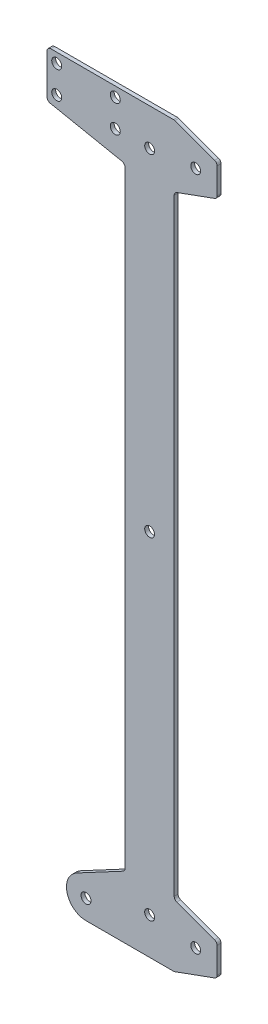
SolidWorks part; units mm, degrees
ref_plane "Front Plane" through (0, 0, 0) normal (0, 0, 1) x (1, 0, 0)
ref_plane "Top Plane" through (0, 0, 0) normal (0, 1, 0) x (1, 0, 0)
ref_plane "Right Plane" through (0, 0, 0) normal (1, 0, 0) x (0, 0, -1)
sketch "Sketch1" plane through (0, 0, 0) normal (0, 0, 1) x (1, 0, 0)
  line L1 (-10, 150) -> (10, 150)
  line L2 (-10, 150) -> (-10, -150)
  line L3 (-10, -150) -> (10, -150)
  line L4 (10, 150) -> (10, -150)
  line L5 (-10, 150) -> (10, -150) construction
  line L6 (-10, -150) -> (10, 150) construction
  point P0 (0, 0)
  dimension "D1" = 300
  dimension "20mm" = 20
extrude "Boss-Extrude1" add sketch "Sketch1" along normal blind 1.5875
sketch "Sketch2" plane through (0, 0, 1.5875) normal (0, 0, 1) x (1, 0, 0)
  line L0 (10, 150) -> (27.4625, 143.65)
  line L1 (27.4625, 143.65) -> (27.4625, 130.95)
  line L2 (27.4625, 130.95) -> (10, 124.6)
  line L3 (10, -150) -> (10, 150) construction
  line L4 (10, 124.6) -> (10, 150)
  line L5 (10, 150) -> (-10, 150) construction
  line L6 (-10, 0) -> (10, 0) construction
  line L7 (-10, 150) -> (-10, -150) construction
  line L8 (10, -124.6) -> (10, -150)
  line L9 (27.4625, -130.95) -> (10, -124.6)
  line L10 (27.4625, -143.65) -> (27.4625, -130.95)
  line L11 (10, -150) -> (27.4625, -143.65)
  line L12 (18.7312, 140.475) -> (18.7312, 134.125) construction
  circle A1 centre (18.7312, 134.125) radius 5 construction
  circle A2 centre (18.7312, 140.475) radius 2 construction
  circle A4 centre (18.7312, -134.125) radius 5 construction
  circle A5 centre (18.7312, -134.125) radius 2 construction
  circle A6 centre (18.7312, 137.3) radius 2
  circle A7 centre (18.7312, -137.3) radius 2
  point P3 (27.4625, 137.3)
  point P8 (10, 137.3)
  point P13 (18.7312, 127.775)
  point P31 (27.4625, -137.3)
  dimension "D3" = 4
  dimension "D4" = 10
  dimension "D1" = 17.4625
  dimension "2.5" = 25.4
  dimension "D2" = 12.7
  dimension "D5" = 9.525
  dimension "D6" = 9.525
extrude "Boss-Extrude2" add sketch "Sketch2" against normal up to surface (1.5875 mm away) up to face at (0, 0, 0)
sketch "Sketch4" plane through (0, 0, 1.5875) normal (0, 0, 1) x (1, 0, 0)
  line L0 (0, 150) -> (0, 135) construction
  line L2 (0, 135) -> (0, 0) construction
  line L3 (0, 0) -> (0, -135) construction
  line L4 (0, -135) -> (0, -150) construction
  line L6 (10, 150) -> (-10, 150) construction
  line L7 (-10, -150) -> (10, -150) construction
  circle A0 centre (0, -135) radius 2
  circle A1 centre (0, 0) radius 2
  circle A2 centre (0, 135) radius 2
  dimension "D4" = 4
  dimension "D1" = 15
  dimension "D2" = 135
  dimension "D3" = 135
extrude "Cut-Extrude1" cut sketch "Sketch4" against normal through all
sketch "Sketch5" plane through (0, 0, 1.5875) normal (0, 0, 1) x (1, 0, 0)
  line L0 (-10, 124.6) -> (-41.75, 130.95)
  line L1 (-10, 150) -> (-10, -150) construction
  line L2 (-41.75, 130.95) -> (-41.75, 150)
  line L3 (-41.75, 150) -> (-10, 150)
  line L4 (-10, 150) -> (-10, 124.6)
  line L5 (10, 150) -> (-10, 150) construction
  line L6 (-41.75, 146.0313) -> (-37.7813, 146.0313) construction
  line L7 (-13.9688, 146.0313) -> (-10, 146.0313) construction
  line L8 (-10, -150) -> (-25.875, -150)
  line L9 (-29.6103, -135.0588) -> (-10, -124.6)
  line L10 (-10, -124.6) -> (-10, -150)
  circle A0 centre (-13.9688, 146.0313) radius 2.032
  circle A1 centre (-13.9688, 134.9188) radius 2.032
  circle A2 centre (-37.7813, 146.0313) radius 2.032
  circle A3 centre (-37.7813, 134.9188) radius 2.032
  arc A4 (-25.875, -150) -> (-29.6103, -135.0588) centre (-25.875, -142.0625) cw
  circle A5 centre (-25.875, -142.0625) radius 2.032
  point P24 (-25.875, 150)
  dimension "D5" = 4.064
  dimension "D9" = 4.064
  dimension "D10" = 7.9375
  dimension "D1" = 0
  dimension "D2" = 19.05
  dimension "D3" = 25.4
  dimension "D4" = 31.75
  dimension "D6" = 11.1125
  dimension "D7" = 23.8125
  dimension "D8" = 3.9688
  dimension "D11" = 25.4
extrude "Boss-Extrude3" add sketch "Sketch5" against normal up to surface (1.5875 mm away) up to face at (2, -135, 0)
fillet "Fillet3" radius 1.5875 11 edges at (-10, -124.6, 0.7937) (27.4625, -143.65, 0.7937) (27.4625, -130.95, 0.7937) (10, -124.6, 0.7937) (27.4625, 130.95, 0.7937) (10, 124.6, 0.7937) (27.4625, 143.65, 0.7937) (10, 150, 0.7937) (-10, 124.6, 0.7937) (-41.75, 130.95, 0.7937) (-41.75, 150, 0.7937)
sketch "Sketch6" [suppressed] plane through (0, 0, 3.175) normal (0, 0, 1) x (1, 0, 0)
  line L0 (-10, -124.6) -> (-10, -150) construction
  line L1 (-10, -150) -> (-25.875, -150) construction
  line L2 (-29.6103, -135.0588) -> (-10, -124.6) construction
  line L3 (-10, -124.6) -> (-10, -150)
  line L4 (-10, -150) -> (-25.875, -150)
  line L5 (-29.6103, -135.0588) -> (-10, -124.6)
  circle A0 centre (-25.875, -142.0625) radius 2.032 construction
  arc A1 (-29.6103, -135.0588) -> (-25.875, -150) centre (-25.875, -142.0625) ccw construction
  circle A2 centre (-25.875, -142.0625) radius 2.032
  arc A3 (-29.6103, -135.0588) -> (-25.875, -150) centre (-25.875, -142.0625) ccw
extrude "Boss-Extrude4" [suppressed] add sketch "Sketch6" against normal up to vertex up to point (-10, -123.6475, 0)
fillet "Fillet4" [suppressed] radius 0.7937
fillet "Fillet5" [suppressed] radius 1.5875
sketch "Sketch7" [suppressed] plane through (0, 0, 0) normal (0, 0, -1) x (-1, 0, 0)
  line L0 (-27.1212, 143.7462) -> (-65.2212, 117.3147)
  line L1 (-65.5625, 116.6625) -> (-65.5625, 8.7125)
  line L2 (-64.9742, 7.9458) -> (-10, -6.7845)
  line L4 (-10, -6.7845) -> (-10, 124.044)
  line L5 (-27.4625, 143.094) -> (-27.4625, 131.506) construction
  line L6 (-26.94, 130.76) -> (-10.5225, 124.79) construction
  line L7 (-27.4625, 143.094) -> (-27.4625, 131.506)
  line L8 (-26.94, 130.76) -> (-10.5225, 124.79)
  line L9 (-10, 150) -> (9.2063, 150) construction
  line L10 (-10, 150) -> (9.2063, 150) construction
  line L11 (-48.989, 45.225) -> (-48.989, 48.4) construction
  line L12 (-38.6703, 23) -> (-59.3078, 23) construction
  line L13 (-38.6703, 23) -> (-38.6703, 67.45) construction
  line L14 (-38.6703, 67.45) -> (-59.3078, 67.45) construction
  line L15 (-59.3078, 23) -> (-59.3078, 67.45) construction
  line L16 (-38.6703, 23) -> (-59.3078, 67.45) construction
  line L17 (-38.6703, 67.45) -> (-59.3078, 23) construction
  line L18 (-48.989, 99.2) -> (-48.989, 48.4) construction
  line L19 (-10, -124.044) -> (-10, 124.044) construction
  arc A0 (-65.2212, 117.3147) -> (-65.5625, 116.6625) centre (-64.7688, 116.6625) ccw
  arc A1 (-65.5625, 8.7125) -> (-64.9742, 7.9458) centre (-64.7687, 8.7125) ccw
  arc A2 (-26.94, 143.84) -> (-27.4625, 143.094) centre (-26.6688, 143.094) ccw construction
  arc A3 (-27.4625, 131.506) -> (-26.94, 130.76) centre (-26.6688, 131.506) ccw construction
  arc A4 (-10, 124.044) -> (-10.5225, 124.79) centre (-10.7937, 124.044) ccw construction
  arc A5 (-27.1212, 143.7462) -> (-27.4625, 143.094) centre (-26.6688, 143.094) ccw
  arc A6 (-27.4625, 131.506) -> (-26.94, 130.76) centre (-26.6688, 131.506) ccw
  arc A7 (-10, 124.044) -> (-10.5225, 124.79) centre (-10.7937, 124.044) ccw
  arc A8 (10, 149.2063) -> (9.2063, 150) centre (9.2063, 149.2063) ccw construction
  circle A9 centre (-48.989, 99.2) radius 4.7625
  circle A10 centre (-48.989, 48.4) radius 6.985
  circle A11 centre (-59.3078, 67.45) radius 2.032
  circle A12 centre (-59.3078, 23) radius 2.032
  circle A13 centre (-38.6703, 23) radius 2.032
  circle A14 centre (-38.6703, 67.45) radius 2.032
  circle A15 centre (-18.7312, 10.3) radius 2.032
  point P32 (-48.989, 45.225)
  point P45 (-18.7312, 137.3)
  dimension "D4" = 9.525
  dimension "D6" = 13.97
  dimension "D11" = 4.064
  dimension "D1" = 38.1
  dimension "D2" = 107.95
  dimension "D3" = 16.5735
  dimension "D5" = 50.8
  dimension "D7" = 3.175
  dimension "D8" = 44.45
  dimension "D9" = 50.8
  dimension "D10" = 20.6375
  dimension "D12" = 75
  dimension "D13" = 127
  dimension "D14" = 33.3375
extrude "Boss-Extrude5" [suppressed] add sketch "Sketch7" against normal up to surface (3.175 mm away) up to face at (2, -135, 1.5875)
sketch "Sketch8" [suppressed] plane through (0, 0, 3.175) normal (0, 0, 1) x (1, 0, 0)
  line L0 (48.989, 48.4) -> (48.989, 67.45) construction
  line L1 (48.989, 48.4) -> (29.939, 48.4) construction
  line L2 (48.989, 48.4) -> (48.989, 29.35) construction
  line L3 (48.989, 99.2) -> (48.989, 108.725) construction
  line L4 (48.989, 99.2) -> (48.989, 89.675) construction
  line L5 (19.6203, 67.45) -> (19.6203, 54.75) construction
  circle A0 centre (48.989, 67.45) radius 2.032
  circle A1 centre (29.939, 48.4) radius 2.032
  circle A2 centre (48.989, 29.35) radius 2.032
  circle A3 centre (59.3078, 67.45) radius 2.032 construction
  circle A4 centre (48.989, 108.725) radius 2.032
  circle A5 centre (48.989, 89.675) radius 2.032
  circle A6 centre (19.6203, 54.75) radius 2.032
  circle A7 centre (19.6203, 67.45) radius 2.032
  dimension "D2" = 9.525
  dimension "D1" = 19.05
  dimension "D3" = 12.7
  dimension "D4" = 6.35
  dimension "D5" = 10.3187
extrude "Cut-Extrude2" [suppressed] cut sketch "Sketch8" against normal through all
